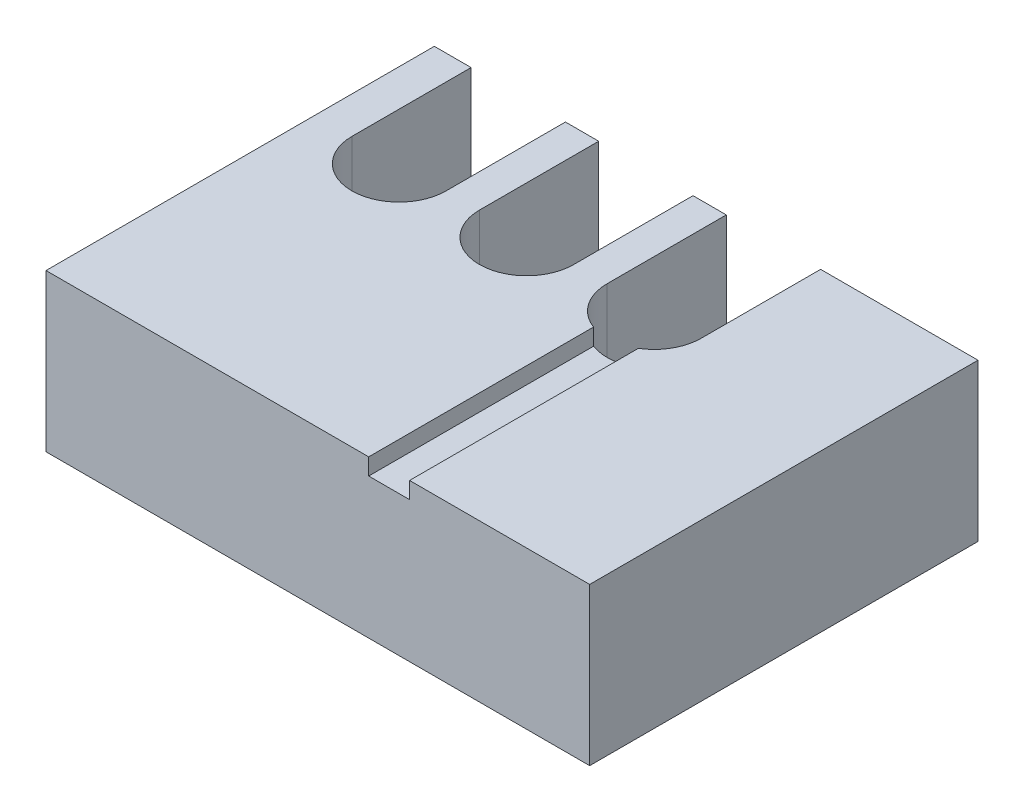
SolidWorks part; units mm, degrees
ref_plane "Ebene vorne" through (0, 0, 0) normal (0, 0, 1) x (1, 0, 0)
ref_plane "Ebene oben" through (0, 0, 0) normal (0, 1, 0) x (1, 0, 0)
ref_plane "Ebene rechts" through (0, 0, 0) normal (1, 0, 0) x (0, 0, -1)
sketch "Skizze1" plane through (0, 0, 0) normal (0, 1, 0) x (1, 0, 0)
  line L1 (0, 0) -> (95, 0)
  line L2 (0, 0) -> (0, 70)
  line L3 (0, 70) -> (95, 70)
  line L4 (95, 0) -> (95, 70)
  dimension "D1" = 95
  dimension "D2" = 70
extrude "Aufsatz-Linear austragen1" add sketch "Skizze1" along normal blind 28.3
sketch "Skizze2" plane through (0, 0, 0) normal (0, 0, 1) x (1, 0, 0)
  line L0 (0, 28.3) -> (95, 28.3) construction
  line L1 (55.17, 28.3) -> (62.54, 28.3)
  line L2 (55.17, 28.3) -> (55.17, 25.3)
  line L3 (55.17, 25.3) -> (62.54, 25.3)
  line L4 (62.54, 28.3) -> (62.54, 25.3)
  line L5 (0, 28.3) -> (0, 0) construction
  dimension "D1" = 7.37
  dimension "D2" = 3
  dimension "D3" = 55.17
extrude "Schnitt-Linear austragen1" cut sketch "Skizze2" against normal up to next
sketch "Skizze4" plane through (0, 0, -70) normal (0, 0, -1) x (-1, 0, 0)
  line L0 (-35.13, 28.3) -> (-35.13, -7.154) construction
  line L1 (-3.63, 0) -> (-71.13, 0)
  line L4 (-71.13, 0) -> (-71.13, 3)
  line L5 (-20.63, 28.3) -> (-3.63, 28.3)
  line L6 (-20.63, 28.3) -> (-20.63, 3)
  line L8 (-3.63, 28.3) -> (-3.63, 3)
  line L9 (-43.63, 28.3) -> (-26.63, 28.3)
  line L10 (-43.63, 28.3) -> (-43.63, 3)
  line L12 (-26.63, 28.3) -> (-26.63, 3)
  line L13 (-66.63, 28.3) -> (-49.63, 28.3)
  line L14 (-66.63, 28.3) -> (-66.63, 3)
  line L16 (-49.63, 28.3) -> (-49.63, 3)
  line L17 (-12.13, 28.3) -> (-12.13, -7.154) construction
  line L18 (-58.13, 28.3) -> (-58.13, -7.154) construction
  line L20 (-95, 0) -> (0, 0) construction
  line L21 (-71.13, 3) -> (-66.63, 3)
  line L22 (-49.63, 3) -> (-43.63, 3)
  line L23 (-26.63, 3) -> (-20.63, 3)
  line L25 (-55.17, 28.3) -> (0, 28.3) construction
  line L26 (0, 28.3) -> (0, 0) construction
  line L27 (-3.63, 0) -> (0, 0)
  line L28 (0, 0) -> (0, 3)
  line L29 (0, 3) -> (-3.63, 3)
  line M26 (-95, 0) -> (0, 0)
  line M27 (0, 0) -> (0, 28.3)
  dimension "D1" = 3.63
  dimension "D2" = 17
  dimension "D3" = 17
  dimension "D4" = 23
  dimension "D5" = 23
  dimension "D6" = 17
  dimension "D7" = 28.3
  dimension "D8" = 13
  dimension "D9" = 3
extrude "Schnitt-Linear austragen2" cut sketch "Skizze4" against normal blind 30 contours L23 L12 L9 L10 L22 L16 L13 L14 L21 L4 L5 L6 M26 M27 region at (35.1917, 13.642, -70)
fillet "Verrundung1" radius 8.5 6 edges at (3.63, 15.65, -40) (20.63, 15.65, -40) (26.63, 15.65, -40) (43.63, 15.65, -40) (49.63, 15.65, -40) (66.63, 15.65, -40)
sketch "Skizze5" plane through (0, 0, 0) normal (-1, 0, 0) x (0, 0, 1)
  line L0 (0, 0) -> (-40, 0)
  line L1 (-40, 0) -> (-40, 3)
  line L2 (-40, 3) -> (-70, 3)
  line L3 (-70, 3) -> (-70, 28.3)
  line L4 (-70, 28.3) -> (0, 28.3)
  line L5 (0, 28.3) -> (0, 0)
extrude "Aufsatz-Linear austragen3" add sketch "Skizze5" along normal blind 3
fillet "Verrundung2" radius 8 1 edges at (71.13, 1.5, -40)
